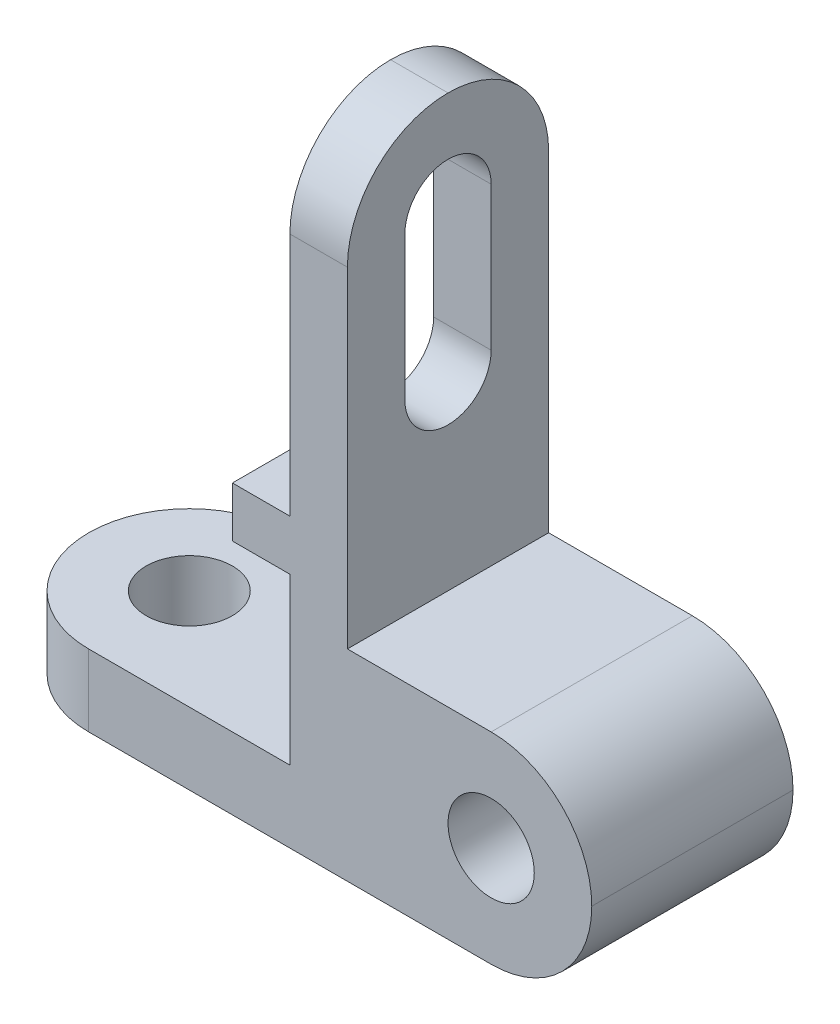
SolidWorks part; units mm, degrees
ref_plane "Front Plane" through (0, 0, 0) normal (0, 0, 1) x (1, 0, 0)
ref_plane "Top Plane" through (0, 0, 0) normal (0, 1, 0) x (1, 0, 0)
ref_plane "Right Plane" through (0, 0, 0) normal (1, 0, 0) x (0, 0, -1)
sketch "Sketch2" plane through (0, 0, 0) normal (0, 0, 1) x (1, 0, 0)
  line L0 (0, 0) -> (0, 28)
  line L1 (0, 28) -> (-34, 28)
  line L2 (-34, 28) -> (-34, 88)
  line L3 (-34, 88) -> (-42, 88)
  line L4 (-42, 88) -> (-42, 40)
  line L5 (-42, 40) -> (-50, 40)
  line L6 (-50, 40) -> (-50, 33)
  line L7 (-50, 33) -> (-42, 33)
  line L8 (-42, 33) -> (-42, 10)
  line L9 (-42, 10) -> (-84, 10)
  line L10 (-84, 10) -> (-84, 0)
  line L11 (-84, 0) -> (0, 0)
  circle A0 centre (-14, 14) radius 6
  point P15 (-70, 10)
  point P16 (-39.5798, 33)
  point P17 (0, 0)
  dimension "D2" = 12
  dimension "D3" = 14
  dimension "D4" = 14
  dimension "D1" = 28
  dimension "D5" = 60
  dimension "D6" = 8
  dimension "D7" = 48
  dimension "D8" = 7
  dimension "D9" = 23
  dimension "D10" = 70
  dimension "D11" = 70
  dimension "D12" = 28
  dimension "D13" = 8
extrude "Boss-Extrude1" add sketch "Sketch2" along normal mid plane 28
sketch "Sketch3" plane through (-34, 0, 0) normal (1, 0, 0) x (0, 0, -1)
  line L0 (0, 54) -> (0, 74) construction
  line L1 (-6, 54) -> (-6, 74)
  line L2 (6, 54) -> (6, 74)
  arc A0 (-6, 54) -> (6, 54) centre (0, 54) ccw
  arc A1 (6, 74) -> (-6, 74) centre (0, 74) ccw
  point P2 (0, 64)
  point P8 (0, 0)
  dimension "D1" = 6
  dimension "D3" = 54
  dimension "D2" = 20
extrude "Cut-Extrude1" cut sketch "Sketch3" against normal up to surface (8 mm away) up to face at (-42, 64, 0)
sketch "Sketch4" plane through (0, 10, 0) normal (0, 1, 0) x (1, 0, 0)
  line L0 (-50, -14) -> (-50, 14) construction
  line L1 (-42, -14) -> (-84, -14) construction
  circle A0 centre (-70, 0) radius 6
  dimension "D1" = 12
  dimension "D2" = 20
  dimension "D3" = 14
extrude "Cut-Extrude2" cut sketch "Sketch4" against normal up to surface (10 mm away) up to face at (-42, 0, 0)
fillet "Fillet1" radius 14 6 edges at (-84, 5, -14) (-84, 5, 14) (-38, 88, -14) (-38, 88, 14) (0, 0, 0) (0, 28, 0)
